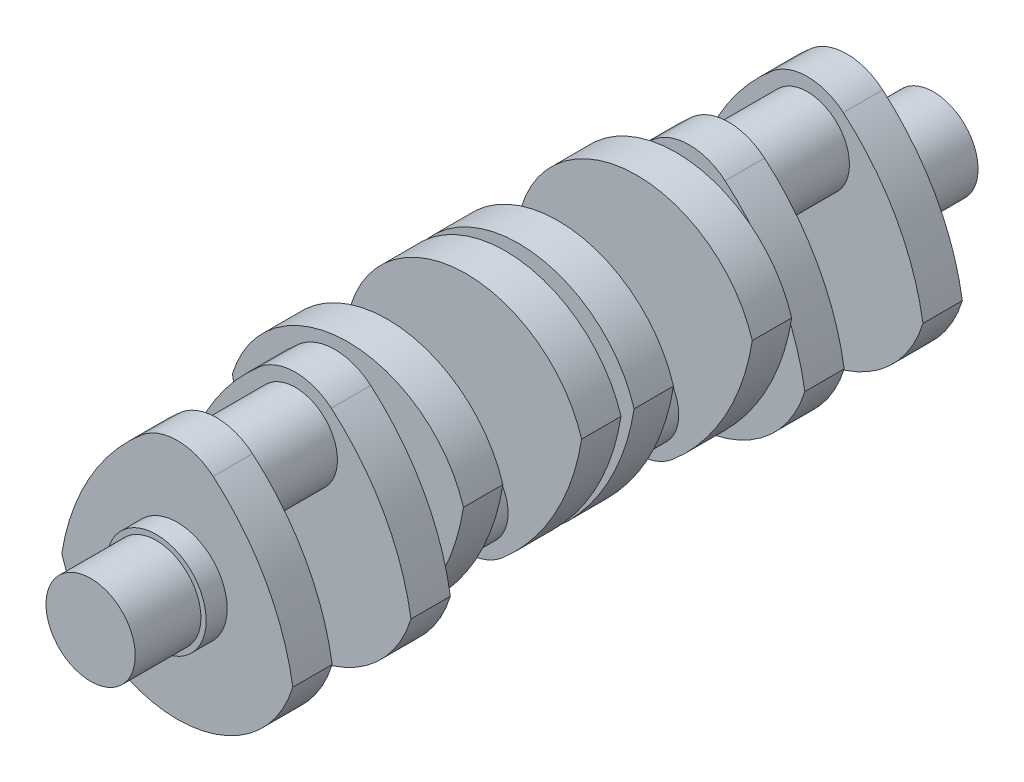
SolidWorks part; units mm, degrees
ref_plane "Front Plane" through (0, 0, 0) normal (0, 0, 1) x (1, 0, 0)
ref_plane "Top Plane" through (0, 0, 0) normal (0, 1, 0) x (1, 0, 0)
ref_plane "Right Plane" through (0, 0, 0) normal (1, 0, 0) x (0, 0, -1)
sketch "Sketch1" plane through (0, 0, 0) normal (0, 0, 1) x (1, 0, 0)
  arc A1 (-13.6681, 40.9431) -> (13.6681, 40.9431) centre (0, 25) cw
  arc A2 (-44, -13.4164) -> (44, -13.4164) centre (0, 0) ccw
  arc A3 (-13.6681, 40.9431) -> (-44, -13.4164) centre (44.9095, -27.3845) ccw
  arc A4 (13.6681, 40.9431) -> (44, -13.4164) centre (-44.9095, -27.3845) cw
  dimension "D1" = 46
  dimension "D2" = 21
  dimension "D4" = 90
  dimension "D5" = 90
  dimension "D3" = 88
  dimension "D6" = 25
extrude "Boss-Extrude1" add sketch "Sketch1" along normal blind 15
sketch "Sketch2" plane through (0, 0, 15) normal (0, 0, 1) x (1, 0, 0)
  circle A0 centre (0, 25) radius 16
  dimension "D1" = 32
  dimension "D2" = 25
extrude "Boss-Extrude2" add sketch "Sketch2" along normal blind 15
ref_plane "Plane1" through (0, 0, 30) normal (0, 0, 1) x (1, 0, 0)
mirror "Mirror4" about plane through (0, 0, 30) normal (0, 0, 1) of "Boss-Extrude2"
mirror "Mirror5" about plane through (0, 0, 30) normal (0, 0, 1) of "Boss-Extrude1"
sketch "Sketch3" plane through (0, 0, 60) normal (0, 0, 1) x (1, 0, 0)
  circle A0 centre (0, 0) radius 17
  dimension "D1" = 34
extrude "Boss-Extrude3" add sketch "Sketch3" along normal blind 5
sketch "Sketch4" plane through (0, 0, 65) normal (0, 0, 1) x (1, 0, 0)
  arc A10 (13.6681, -40.9431) -> (44, 13.4164) centre (-44.9095, 27.3845) ccw
  arc A11 (44, 13.4164) -> (-44, 13.4164) centre (0, 0) ccw
  arc A12 (-44, 13.4164) -> (-13.6681, -40.9431) centre (44.9095, 27.3845) ccw
  arc A13 (-13.6681, -40.9431) -> (13.6681, -40.9431) centre (0, -25) ccw
extrude "Boss-Extrude4" add sketch "Sketch4" along normal blind 15
sketch "Sketch5" plane through (0, 0, 80) normal (0, 0, 1) x (1, 0, 0)
  circle A0 centre (0, -25) radius 16
  dimension "D1" = 32
  dimension "D2" = 25
extrude "Boss-Extrude5" add sketch "Sketch5" along normal blind 30
sketch "Sketch6" plane through (0, 0, 110) normal (0, 0, 1) x (1, 0, 0)
  arc A6 (-13.6681, -40.9431) -> (13.6681, -40.9431) centre (0, -25) ccw
  arc A7 (13.6681, -40.9431) -> (44, 13.4164) centre (-44.9095, 27.3845) ccw
  arc A8 (44, 13.4164) -> (-44, 13.4164) centre (0, 0) ccw
  arc A9 (-44, 13.4164) -> (-13.6681, -40.9431) centre (44.9095, 27.3845) ccw
  arc A10 (-13.6681, -40.9431) -> (13.6681, -40.9431) centre (0, -25) ccw
  arc A11 (13.6681, -40.9431) -> (44, 13.4164) centre (-44.9095, 27.3845) ccw
  arc A12 (44, 13.4164) -> (-44, 13.4164) centre (0, 0) ccw
  arc A13 (-44, 13.4164) -> (-13.6681, -40.9431) centre (44.9095, 27.3845) ccw
  dimension "D2" = 0
extrude "Boss-Extrude7" add sketch "Sketch6" along normal blind 15
sketch "Sketch7" plane through (0, 0, 125) normal (0, 0, 1) x (1, 0, 0)
  circle A0 centre (0, 0) radius 17
  dimension "D1" = 34
extrude "Boss-Extrude8" add sketch "Sketch7" along normal blind 2.5
sketch "Sketch8" plane through (0, 0, 0) normal (0, 0, -1) x (-1, 0, 0)
  circle A0 centre (0, 0) radius 19
  circle A1 centre (0, 0) radius 17
  dimension "D1" = 38
  dimension "D2" = 34
extrude "Boss-Extrude9" add sketch "Sketch8" along normal blind 8 contours A1 | A0 A1 region at (18.4626, 0, 0) region at (0, 0, 0)
extrude "Boss-Extrude10" add sketch "Sketch8<3>" along normal blind 25 from offset 8 contours A1 region at (0, 0, 0)
sketch "Sketch8<3>" plane through (0, 0, 0) normal (0, 0, -1) x (-1, 0, 0) same geometry as "Sketch8"
mirror "Mirror6" about plane through (0, 0, 127.5) normal (0, 0, 1) of bodies 115
